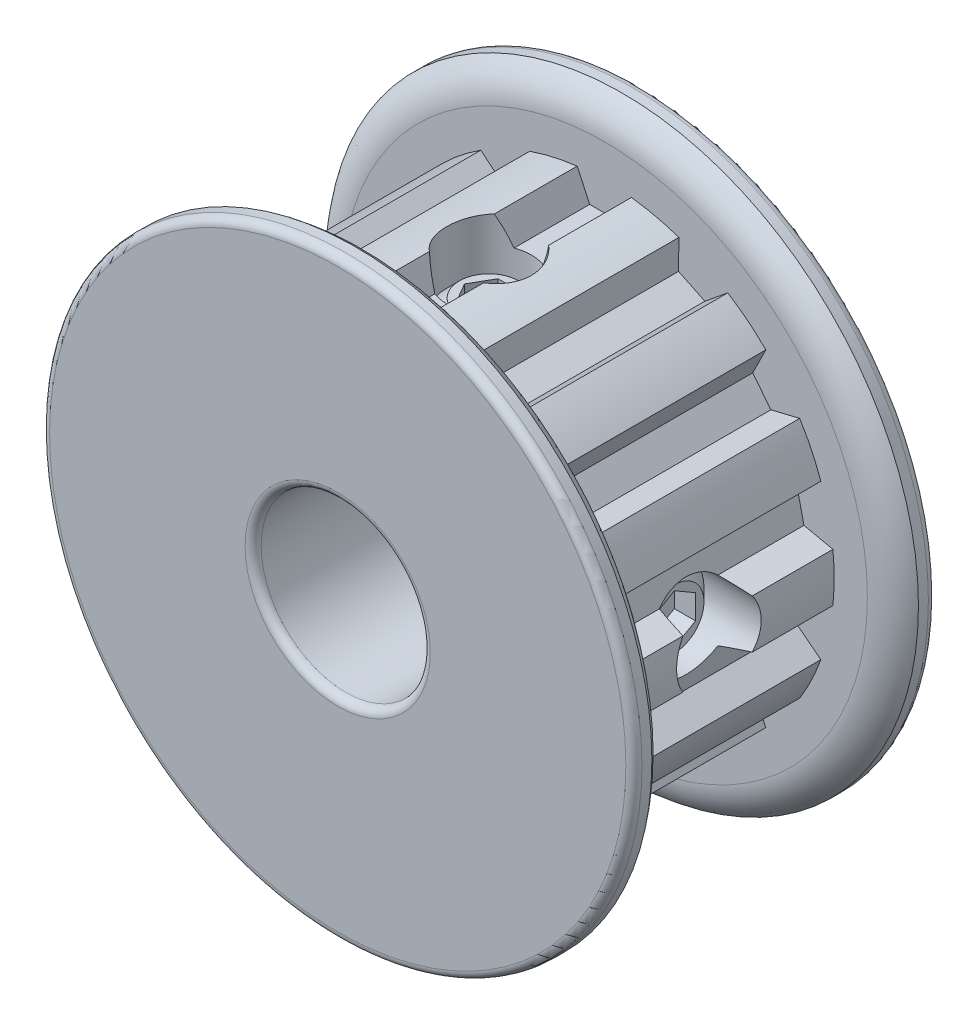
SolidWorks part; units mm, degrees
ref_plane "Front Plane" through (0, 0, 0) normal (0, 0, 1) x (1, 0, 0)
ref_plane "Top Plane" through (0, 0, 0) normal (0, 1, 0) x (1, 0, 0)
ref_plane "Right Plane" through (0, 0, 0) normal (1, 0, 0) x (0, 0, -1)
sketch "Sketch1" plane through (0, 0, 0) normal (0, 0, 1) x (1, 0, 0)
  line L0 (-1.2827, 10.792) -> (-0.6905, 9.522)
  line L1 (-0.6905, 9.522) -> (0.6905, 9.522)
  line L2 (0.6905, 9.522) -> (1.2827, 10.792)
  line L3 (-1.2827, 10.792) -> (1.2827, 10.792)
  line L4 (0, 0) -> (0, 9.522) construction
  line L5 (0, 9.522) -> (0, 11.808) construction
  circle A0 centre (0, 0) radius 11.3 construction
  circle A1 centre (0, 0) radius 14 construction
  circle A2 centre (0, 0) radius 10.868 construction
  point P6 (0, 10.792)
  point P11 (0, 11.3)
  point P13 (0, 14)
  point P14 (0, 10.868)
  dimension "D1" = 1.016
  dimension "PD" = 22.6
  dimension "D2" = 0.508
  dimension "OD" = 28
  dimension "b" = 50
  dimension "bt" = 2.5654
  dimension "ht" = 1.27
  dimension "hs" = 2.286
sketch "Sketch2" plane through (0, 0, 0) normal (1, 0, 0) x (0, 0, -1)
  line L0 (-7.15, 4) -> (7.15, 4)
  line L3 (-7.15, 4) -> (-7.15, 14)
  line L4 (-7.15, 14) -> (-5.45, 14) construction
  line L5 (-5.45, 14) -> (-5.45, 10.868) construction
  line L6 (-5.45, 10.868) -> (5.45, 10.868)
  line L7 (5.45, 10.868) -> (5.45, 14) construction
  line L8 (5.45, 14) -> (7.15, 14) construction
  line L9 (7.15, 14) -> (7.15, 4)
  line L10 (-7.15, 0) -> (7.15, 0) construction
  line L13 (-7.15, 14) -> (-6.3, 14)
  line L14 (-5.45, 12.434) -> (-5.45, 10.868)
  line L15 (5.45, 10.868) -> (5.45, 12.434)
  line L16 (6.3, 14) -> (7.15, 14)
  arc A0 (-5.45, 12.434) -> (-6.3, 14) centre (-7.3176, 12.434) ccw
  arc A1 (5.45, 12.434) -> (6.3, 14) centre (7.3176, 12.434) cw
  point P12 (-5.45, 12.434)
  point P14 (-6.3, 14)
  point P20 (5.45, 12.434)
  point P21 (6.3, 14)
  point P25 (5.45, 0)
  point P26 (-5.45, 0)
  dimension "OA" = 14.3
  dimension "Bore" = 8
  dimension "Outside Width" = 14.3
  dimension "Inside Width" = 10.9
revolve "Revolve1" add sketch "Sketch2" angle 360 mid plane about L10
sketch "Sketch3" plane through (0, 0, 0) normal (0, 0, 1) x (1, 0, 0)
  line L0 (-0.6905, 9.522) -> (0.6905, 9.522) construction
  line L1 (0.6905, 9.522) -> (1.2827, 10.792) construction
  line L2 (-1.2827, 10.792) -> (-0.6905, 9.522) construction
  line L3 (-0.6905, 9.522) -> (0.6905, 9.522)
  line L4 (0.6905, 9.522) -> (1.2827, 10.792)
  line L5 (-1.2827, 10.792) -> (-0.6905, 9.522)
  circle A0 centre (0, 0) radius 10.868 construction
  arc A1 (1.2827, 10.792) -> (-1.2827, 10.792) centre (0, 0) ccw
extrude "Cut-Extrude1" cut sketch "Sketch3" against normal up to vertex (5.45 mm away) from vertex up to point (0, 10.868, -5.45) starting at point (0, 10.868, 5.45)
pattern_circular "CirPattern1" count 14 over 360 about axis through (0, 0, 7.15) along (0, 0, 1) of "Cut-Extrude1"
fillet "Fillet1" radius 0.381 4 edges at (4, 0, -7.15) (14, 0, -7.15) (14, 0, 7.15) (4, 0, 7.15)
sketch "Sketch5" plane through (0, 0, 0) normal (0, 1, 0) x (1, 0, 0)
  line L1 (1.2827, 0) -> (-1.2827, 0) construction
  line L2 (1.2827, 5.45) -> (1.2827, -5.45) construction
  line L3 (-1.2827, 5.45) -> (-1.2827, -5.45) construction
  circle A0 centre (0, 0) radius 2
extrude "Cut-Extrude2" cut sketch "Sketch5" along normal through all
sketch "Sketch6" plane through (0, 0, 0) normal (1, 0, 0) x (0, 0, -1)
  line L0 (0, 8.76) -> (0, 4.762)
  line L1 (6.769, 4) -> (-6.769, 4) construction
  line L3 (2, 9.522) -> (-2, 9.522) construction
  line L4 (-1.877, 9.522) -> (-2, 9.522) construction
  line L5 (2, 9.522) -> (1.877, 9.522) construction
  line L6 (0, 8.76) -> (-1.4, 8.76)
  line L7 (-1.4, 8.76) -> (-2, 8.16)
  line L8 (-2, 8.16) -> (-2, 5.362)
  line L9 (-2, 5.362) -> (-1.4, 4.762)
  line L10 (-1.4, 4.762) -> (0, 4.762)
  point P12 (0, 4)
  point P19 (0, 9.522)
  dimension "D1" = 0.762
  dimension "D2" = 0.762
  dimension "D3" = 135
revolve "Revolve2" add sketch "Sketch6" angle 360 about L0
sketch "Sketch7" plane through (0, 8.76, 0) normal (0, 1, 0) x (1, 0, 0)
  line L1 (1.1547, 0) -> (0.5774, 1)
  line L2 (0.5774, 1) -> (-0.5774, 1)
  line L3 (-0.5774, 1) -> (-1.1547, 0)
  line L4 (-1.1547, 0) -> (-0.5774, -1)
  line L5 (-0.5774, -1) -> (0.5774, -1)
  line L6 (0.5774, -1) -> (1.1547, 0)
  circle A0 centre (0, 0) radius 1 construction
  dimension "D1" = 2
extrude "Cut-Extrude3" cut sketch "Sketch7" against normal blind 1
pattern_circular "CirPattern2" count 2 over 270 of "Cut-Extrude2", "Revolve2", "Cut-Extrude3"
ref_axis "Center Axis 1" through (0, 0, -6.769) along (0, 0, 1)
ref_plane "Contact Plane 1" through (0, 0, 7.15) normal (0, 0, 1) x (1, 0, 0)
ref_plane "Contact Plane 2" through (0, 0, -7.15) normal (0, 0, -1) x (-1, 0, 0)
equation "\"D4@Sketch6\" = \"Set Screw Dia@Sketch5\" * .15"
equation "\"D1@Sketch7\" = \"Set Screw Dia@Sketch5\" / 2"
equation "\"D1@Cut-Extrude3\" = \"Set Screw Dia@Sketch5\" / 4"
